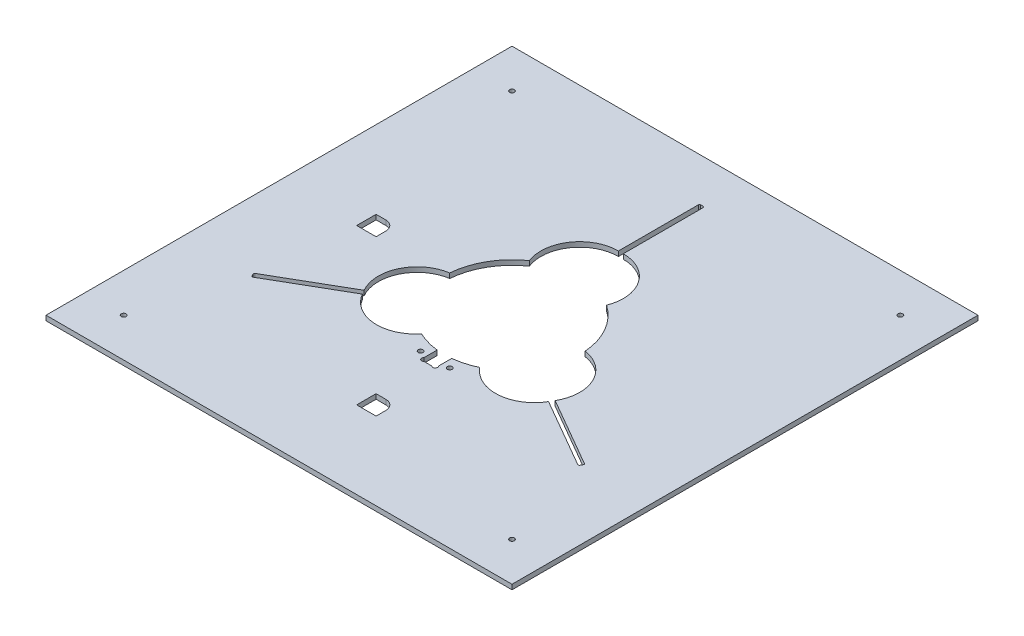
SolidWorks part; units mm, degrees
ref_plane "Front Plane" through (0, 0, 0) normal (0, 0, 1) x (1, 0, 0)
ref_plane "Top Plane" through (0, 0, 0) normal (0, 1, 0) x (1, 0, 0)
ref_plane "Right Plane" through (0, 0, 0) normal (1, 0, 0) x (0, 0, -1)
sketch "Sketch1" plane through (0, 0, 0) normal (0, 1, 0) x (1, 0, 0)
  line L1 (-304.8, -304.8) -> (304.8, -304.8)
  line L2 (-304.8, -304.8) -> (-304.8, 304.8)
  line L3 (-304.8, 304.8) -> (304.8, 304.8)
  line L4 (304.8, -304.8) -> (304.8, 304.8)
  line L5 (0, 304.8) -> (0, -304.8) construction
  line L6 (-304.8, 0) -> (304.8, 0) construction
  point P0 (0, 0)
  dimension "D1" = 609.6
  dimension "D2" = 609.6
extrude "Boss-Extrude1" add sketch "Sketch1" along normal blind 6.35 contours L2 L3 L4 L1
sketch "Sketch3" plane through (0, 0, 0) normal (0, 1, 0) x (1, 0, 0)
  line L0 (0, 0) -> (0, 332.7806) construction
  line L1 (0, 0) -> (-286.8222, -165.5969) construction
  line L2 (0, 0) -> (289.9079, -167.3784) construction
  line L3 (-3.175, 248.4755) -> (-3.175, 142.4547)
  line L4 (-50.4923, 73.1692) -> (50.4923, 73.1692) construction
  line L5 (-3.175, 248.4755) -> (3.175, 248.4755)
  line L6 (213.5986, -126.9874) -> (121.7819, -73.977)
  line L7 (3.175, 248.4755) -> (3.175, 142.4547)
  line L8 (216.7736, -121.4881) -> (124.9569, -68.4777)
  line L9 (216.7736, -121.4881) -> (213.5986, -126.9874)
  line L10 (-216.7736, -121.4881) -> (-124.9569, -68.4777)
  line L11 (-213.5986, -126.9874) -> (-121.7819, -73.977)
  line L12 (-213.5986, -126.9874) -> (-216.7736, -121.4881)
  line L20 (-3.175, 142.4547) -> (3.175, 142.4547) construction
  arc A0 (88.6126, 7.143) -> (50.4923, 73.1692) centre (0, 0) ccw
  arc A1 (-3.175, 142.4547) -> (-50.4923, 73.1692) centre (-3.175, 91.6547) ccw
  arc A2 (3.175, 142.4547) -> (50.4923, 73.1692) centre (3.175, 91.6547) cw
  arc A3 (-50.4923, 73.1692) -> (-88.6126, 7.143) centre (0, 0) ccw
  arc A4 (121.7819, -73.977) -> (38.1203, -80.3122) centre (77.7878, -48.577) cw
  arc A5 (124.9569, -68.4777) -> (88.6126, 7.143) centre (80.9628, -43.0777) ccw
  arc A6 (-38.1203, -80.3122) -> (38.1203, -80.3122) centre (0, 0) ccw
  arc A7 (-124.9569, -68.4777) -> (-88.6126, 7.143) centre (-80.9628, -43.0777) cw
  arc A8 (-121.7819, -73.977) -> (-38.1203, -80.3122) centre (-77.7878, -48.577) ccw
  point P3 (0, 169.3508)
  point P17 (0, 83.82)
  point P33 (0, 0)
  point P34 (0, 0)
  point P37 (0, 0)
  point P62 (0, 0)
  dimension "D6" = 88.9
  dimension "D7" = 50.8
  dimension "D11" = 6.35
  dimension "D16" = 83.82
  dimension "D10" = 100.9846
  dimension "D2" = 120
  dimension "D3" = 120
  dimension "D4" = 6.35
  dimension "D5" = 164.6555
  dimension "D8" = 3
extrude "Cut-Extrude2" cut sketch "Sketch3" along normal through all
sketch "Sketch4" plane through (0, 0, 0) normal (0, 1, 0) x (1, 0, 0)
  line L0 (0, 0) -> (-203.2, 0) construction
  line L1 (0, 0) -> (0, -203.2) construction
  line L3 (0, -203.2) -> (25.4, -203.2)
  line L4 (0, -203.2) -> (0, -177.8)
  line L5 (0, -177.8) -> (25.4, -177.8)
  line L6 (25.4, -203.2) -> (25.4, -177.8)
  line L7 (-203.2, 0) -> (-177.8, 0)
  line L8 (-203.2, 0) -> (-203.2, 25.4)
  line L9 (-203.2, 25.4) -> (-177.8, 25.4)
  line L10 (-177.8, 0) -> (-177.8, 25.4)
  dimension "D1" = 203.2
  dimension "D2" = 203.2
  dimension "D3" = 25.4
  dimension "D4" = 25.4
  dimension "D5" = 25.4
  dimension "D6" = 25.4
extrude "Cut-Extrude8" cut sketch "Sketch4" along normal through all
fillet "Fillet4" radius 12.7 1 edges at (-177.8, 3.175, -25.4)
fillet "Fillet5" radius 12.7 1 edges at (25.4, 3.175, 177.8)
sketch "Sketch5" plane through (0, 6.35, 0) normal (0, 1, 0) x (1, 0, 0)
  line L1 (-254, -254) -> (254, -254) construction
  line L2 (-254, -254) -> (-254, 254) construction
  line L3 (-254, 254) -> (254, 254) construction
  line L4 (254, -254) -> (254, 254) construction
  line L5 (0, 254) -> (0, -254) construction
  line L6 (-254, 0) -> (254, 0) construction
  circle A0 centre (-254, 254) radius 3.175
  circle A1 centre (254, 254) radius 3.175
  circle A2 centre (254, -254) radius 3.175
  circle A3 centre (-254, -254) radius 3.175
  point P0 (0, 0)
  dimension "D3" = 6.35
  dimension "D1" = 508
  dimension "D2" = 508
  dimension "D4" = 2
  dimension "D5" = 2
extrude "Cut-Extrude9" cut sketch "Sketch5" against normal through all
fillet "Fillet9" radius 1.5875 6 edges at (216.7736, 3.175, 121.4881) (213.5986, 3.175, 126.9874) (-216.7736, 3.175, 121.4881) (-213.5986, 3.175, 126.9874) (3.175, 3.175, -248.4755) (-3.175, 3.175, -248.4755)
sketch "Sketch6" plane through (0, 6.35, 0) normal (0, 1, 0) x (1, 0, 0)
  line L0 (0, -83.82) -> (0, -90.932) construction
  line L1 (0, -90.932) -> (0, -109.982) construction
  line L2 (9.525, -109.982) -> (9.525, -105.4919) construction
  line L3 (9.525, -109.982) -> (19.05, -109.982) construction
  line L4 (19.05, -109.982) -> (19.05, -103.632) construction
  line L5 (19.05, -103.632) -> (19.05, -100.457) construction
  line L6 (15.875, -100.457) -> (9.525, -100.457) construction
  line L7 (-9.525, -100.457) -> (-9.525, -83.277)
  line L8 (-9.525, -100.457) -> (-9.525, -105.4919)
  line L9 (-9.525, -83.277) -> (9.525, -83.277)
  line L10 (5.0349, -109.982) -> (9.525, -109.982) construction
  line L11 (-5.0349, -109.982) -> (5.0349, -109.982)
  line L12 (9.525, -100.457) -> (9.525, -83.277)
  line L13 (9.525, -100.457) -> (9.525, -105.4919)
  circle A0 centre (0, 0) radius 83.82 construction
  circle A1 centre (19.05, -100.457) radius 3.175
  circle A2 centre (-19.05, -100.457) radius 3.175
  arc A3 (5.0349, -109.982) -> (9.525, -105.4919) centre (7.2799, -107.7369) ccw
  arc A4 (-5.0349, -109.982) -> (-9.525, -105.4919) centre (-7.2799, -107.7369) cw
  point P22 (9.525, -109.982)
  dimension "D1" = 6.35
  dimension "D4" = 167.64
  dimension "D8" = 3.175
  dimension "D2" = 6.35
  dimension "D3" = 7.112
  dimension "D5" = 19.05
  dimension "D6" = 6.35
  dimension "D7" = 9.525
extrude "Cut-Extrude10" cut sketch "Sketch6" against normal through all
